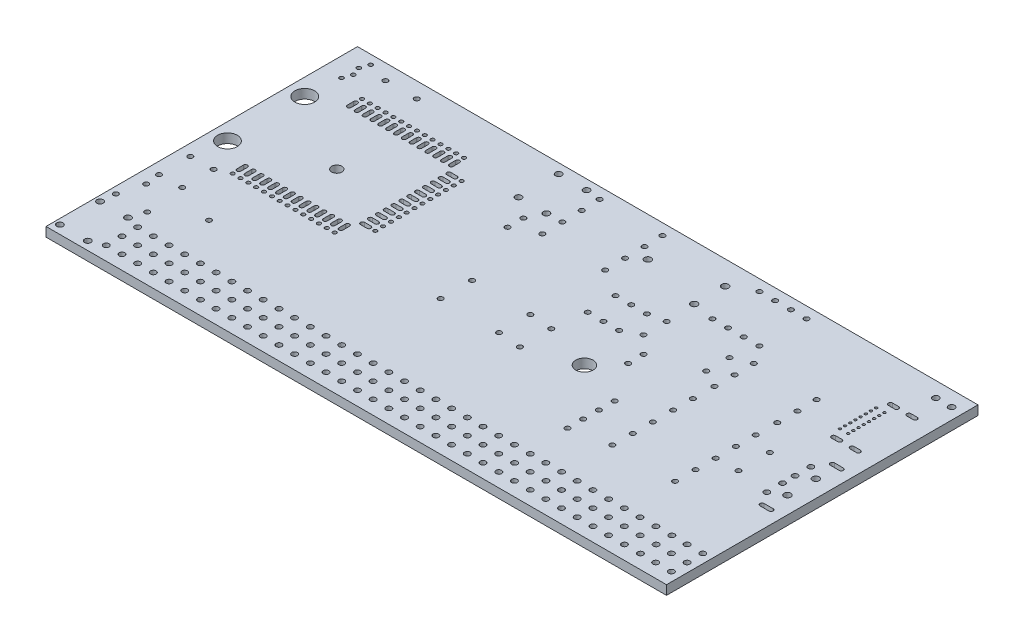
SolidWorks part; units mm, degrees
ref_plane "Front Plane" through (0, 0, 0) normal (0, 0, 1) x (1, 0, 0)
ref_plane "Top Plane" through (0, 0, 0) normal (0, 1, 0) x (1, 0, 0)
ref_plane "Right Plane" through (0, 0, 0) normal (1, 0, 0) x (0, 0, -1)
sketch "Sketch1" plane through (0, 0, 0) normal (0, 1, 0) x (1, 0, 0)
  line L0 (-55, 0) -> (55, 0) construction
  line L1 (0, -55) -> (0, 55) construction
  line B0 (9.071, 43.739) -> (9.071, 43.039) construction
  line B1 (9.071, 43.039) -> (9.071, 41.339) construction
  line B2 (28.626, 40.304) -> (27.926, 40.304) construction
  line B3 (27.926, 40.304) -> (26.226, 40.304) construction
  line B4 (1.375, 50.708) -> (1.375, 0.308)
  line B5 (1.375, 0.308) -> (101.775, 0.308)
  line B6 (101.775, 0.308) -> (101.775, 50.708)
  line B7 (101.775, 50.708) -> (1.375, 50.708)
  line B8 (9.071, 22.809) -> (9.071, 23.509) construction
  line B9 (9.071, 23.509) -> (9.071, 25.209) construction
  line B10 (99.7365, 30.632) -> (98.2815, 30.632) construction
  line B11 (98.2815, 30.632) -> (98.2815, 30.961) construction
  circle B12 centre (4.0919, 39.4542) radius 1.5922
  circle B13 centre (95.301, 42.05) radius 0.203
  circle B14 centre (95.301, 41.212) radius 0.203
  circle B15 centre (95.301, 38.697) radius 0.203
  circle B16 centre (95.301, 37.859) radius 0.203
  circle B17 centre (95.301, 40.373) radius 0.203
  circle B18 centre (95.301, 39.535) radius 0.203
  circle B19 centre (93.955, 42.05) radius 0.203
  circle B20 centre (93.955, 41.212) radius 0.203
  circle B21 centre (93.955, 40.373) radius 0.203
  circle B22 centre (93.955, 37.859) radius 0.203
  circle B23 centre (93.955, 37.02) radius 0.203
  circle B24 centre (93.955, 39.535) radius 0.203
  circle B25 centre (93.955, 38.697) radius 0.203
  circle B26 centre (96.926, 28.499) radius 0.45
  circle B27 centre (95.301, 37.02) radius 0.203
  circle B28 centre (95.301, 36.182) radius 0.203
  circle B29 centre (99.009, 27.229) radius 0.546
  circle B30 centre (99.009, 22.644) radius 0.546
  circle B31 centre (96.926, 25.959) radius 0.45
  circle B32 centre (96.926, 23.927) radius 0.45
  circle B33 centre (93.955, 36.182) radius 0.203
  circle B34 centre (88.036, 35.23) radius 0.406
  circle B35 centre (88.034, 31.965) radius 0.406
  circle B36 centre (91.618, 27.178) radius 0.406
  circle B37 centre (91.618, 22.098) radius 0.406
  circle B38 centre (88.011, 25.298) radius 0.406
  circle B39 centre (88.036, 22.003) radius 0.406
  circle B40 centre (75.844, 48.895) radius 0.406
  circle B41 centre (73.304, 48.895) radius 0.406
  circle B42 centre (75.844, 41.275) radius 0.406
  circle B43 centre (70.764, 48.895) radius 0.406
  circle B44 centre (70.764, 41.275) radius 0.406
  circle B45 centre (77.826, 38.379) radius 0.406
  circle B46 centre (87.986, 38.379) radius 0.406
  circle B47 centre (73.304, 41.275) radius 0.406
  circle B48 centre (75.057, 37.211) radius 0.406
  circle B49 centre (68.224, 48.895) radius 0.406
  circle B50 centre (64.7, 46.874) radius 0.546
  circle B51 centre (54.69, 44.374) radius 0.546
  circle B52 centre (64.68, 41.874) radius 0.546
  circle B53 centre (68.224, 41.275) radius 0.406
  circle B54 centre (64.897, 37.211) radius 0.406
  circle B55 centre (59.69, 36.678) radius 0.406
  circle B56 centre (62.23, 36.678) radius 0.406
  circle B57 centre (77.876, 35.23) radius 0.406
  circle B58 centre (77.874, 31.965) radius 0.406
  circle B59 centre (88.001, 28.512) radius 0.406
  circle B60 centre (75.057, 33.452) radius 0.406
  circle B61 centre (77.841, 28.512) radius 0.406
  circle B62 centre (77.851, 25.298) radius 0.406
  circle B63 centre (77.876, 22.003) radius 0.406
  circle B64 centre (67.666, 28.194) radius 0.406
  circle B65 centre (71.832, 21.846) radius 0.406
  circle B66 centre (64.897, 33.452) radius 0.406
  circle B67 centre (62.306, 32.106) radius 0.406
  circle B68 centre (57.15, 36.678) radius 0.406
  circle B69 centre (59.766, 32.106) radius 0.406
  circle B70 centre (67.64, 30.734) radius 0.406
  circle B71 centre (64.364, 24.435) radius 1.4
  circle B72 centre (57.226, 32.106) radius 0.406
  circle B73 centre (56.591, 26.848) radius 0.406
  circle B74 centre (96.926, 21.387) radius 0.45
  circle B75 centre (95.301, 7.645) radius 0.457
  circle B76 centre (88.011, 18.771) radius 0.406
  circle B77 centre (90.17, 7.62) radius 0.457
  circle B78 centre (97.79, 7.62) radius 0.457
  circle B79 centre (100.33, 7.62) radius 0.457
  circle B80 centre (92.735, 7.62) radius 0.457
  circle B81 centre (95.301, 5.105) radius 0.457
  circle B82 centre (77.851, 18.771) radius 0.406
  circle B83 centre (87.981, 15.489) radius 0.406
  circle B84 centre (77.821, 15.489) radius 0.406
  circle B85 centre (77.47, 7.645) radius 0.457
  circle B86 centre (85.09, 7.62) radius 0.457
  circle B87 centre (87.63, 7.62) radius 0.457
  circle B88 centre (80.01, 7.62) radius 0.457
  circle B89 centre (82.55, 7.62) radius 0.457
  circle B90 centre (100.33, 5.08) radius 0.457
  circle B91 centre (97.79, 5.08) radius 0.457
  circle B92 centre (95.301, 2.565) radius 0.457
  circle B93 centre (90.17, 5.08) radius 0.457
  circle B94 centre (92.735, 5.08) radius 0.457
  circle B95 centre (97.79, 2.54) radius 0.457
  circle B96 centre (100.33, 2.54) radius 0.457
  circle B97 centre (90.17, 2.54) radius 0.457
  circle B98 centre (92.735, 2.54) radius 0.457
  circle B99 centre (85.09, 5.08) radius 0.457
  circle B100 centre (87.63, 5.08) radius 0.457
  circle B101 centre (80.01, 5.08) radius 0.457
  circle B102 centre (82.55, 5.08) radius 0.457
  circle B103 centre (85.09, 2.54) radius 0.457
  circle B104 centre (87.63, 2.54) radius 0.457
  circle B105 centre (80.01, 2.54) radius 0.457
  circle B106 centre (82.55, 2.54) radius 0.457
  circle B107 centre (72.415, 7.62) radius 0.457
  circle B108 centre (71.832, 14.226) radius 0.406
  circle B109 centre (74.93, 7.62) radius 0.457
  circle B110 centre (71.832, 19.306) radius 0.406
  circle B111 centre (71.832, 16.766) radius 0.406
  circle B112 centre (77.47, 5.105) radius 0.457
  circle B113 centre (72.415, 5.08) radius 0.457
  circle B114 centre (69.85, 7.62) radius 0.457
  circle B115 centre (69.85, 5.08) radius 0.457
  circle B116 centre (64.77, 7.62) radius 0.457
  circle B117 centre (67.31, 7.62) radius 0.457
  circle B118 centre (56.591, 21.768) radius 0.406
  circle B119 centre (62.23, 7.62) radius 0.457
  circle B120 centre (59.69, 7.62) radius 0.457
  circle B121 centre (67.31, 5.08) radius 0.457
  circle B122 centre (54.61, 7.62) radius 0.457
  circle B123 centre (57.15, 7.62) radius 0.457
  circle B124 centre (74.93, 5.08) radius 0.457
  circle B125 centre (77.47, 2.565) radius 0.457
  circle B126 centre (64.77, 5.08) radius 0.457
  circle B127 centre (74.93, 2.54) radius 0.457
  circle B128 centre (69.85, 2.54) radius 0.457
  circle B129 centre (72.415, 2.54) radius 0.457
  circle B130 centre (64.77, 2.54) radius 0.457
  circle B131 centre (67.31, 2.54) radius 0.457
  circle B132 centre (59.69, 5.08) radius 0.457
  circle B133 centre (62.23, 5.08) radius 0.457
  circle B134 centre (54.61, 5.08) radius 0.457
  circle B135 centre (57.15, 5.08) radius 0.457
  circle B136 centre (59.69, 2.54) radius 0.457
  circle B137 centre (62.23, 2.54) radius 0.457
  circle B138 centre (54.61, 2.54) radius 0.457
  circle B139 centre (57.15, 2.54) radius 0.457
  circle B140 centre (52.629, 45.898) radius 0.406
  circle B141 centre (52.527, 48.895) radius 0.406
  circle B142 centre (42.469, 45.898) radius 0.406
  circle B143 centre (40.03, 49.124) radius 0.508
  circle B144 centre (42.367, 48.895) radius 0.406
  circle B145 centre (52.68, 42.697) radius 0.406
  circle B146 centre (52.73, 39.421) radius 0.406
  circle B147 centre (42.52, 42.697) radius 0.406
  circle B148 centre (42.57, 39.421) radius 0.406
  circle B149 centre (35.509, 49.124) radius 0.508
  circle B150 centre (40.03, 42.621) radius 0.508
  circle B151 centre (24.311, 43.739) radius 0.3
  circle B152 centre (25.581, 43.739) radius 0.3
  circle B153 centre (35.509, 42.621) radius 0.508
  circle B154 centre (38.837, 40.081) radius 0.406
  circle B155 centre (28.626, 40.304) radius 0.3
  circle B156 centre (28.626, 39.034) radius 0.3
  circle B157 centre (38.837, 37.541) radius 0.406
  circle B158 centre (28.626, 36.494) radius 0.3
  circle B159 centre (28.626, 35.224) radius 0.3
  circle B160 centre (28.626, 33.954) radius 0.3
  circle B161 centre (28.626, 32.684) radius 0.3
  circle B162 centre (43.409, 27.203) radius 0.406
  circle B163 centre (52.908, 27.153) radius 0.406
  circle B164 centre (28.626, 31.414) radius 0.3
  circle B165 centre (43.409, 22.123) radius 0.406
  circle B166 centre (28.626, 28.874) radius 0.3
  circle B167 centre (28.626, 27.604) radius 0.3
  circle B168 centre (28.626, 37.764) radius 0.3
  circle B169 centre (28.626, 30.144) radius 0.3
  circle B170 centre (28.626, 26.334) radius 0.3
  circle B171 centre (25.581, 22.809) radius 0.3
  circle B172 centre (23.041, 22.809) radius 0.3
  circle B173 centre (24.311, 22.809) radius 0.3
  circle B174 centre (16.691, 43.739) radius 0.3
  circle B175 centre (15.421, 43.739) radius 0.3
  circle B176 centre (17.961, 43.739) radius 0.3
  circle B177 centre (13.487, 48.184) radius 0.406
  circle B178 centre (14.151, 43.739) radius 0.3
  circle B179 centre (21.771, 43.739) radius 0.3
  circle B180 centre (23.041, 43.739) radius 0.3
  circle B181 centre (19.231, 43.739) radius 0.3
  circle B182 centre (20.501, 43.739) radius 0.3
  circle B183 centre (4.98, 49.219) radius 0.325
  circle B184 centre (8.407, 48.184) radius 0.406
  circle B185 centre (4.472, 47.822) radius 0.325
  circle B186 centre (4.98, 46.425) radius 0.325
  circle B187 centre (11.611, 43.739) radius 0.3
  circle B188 centre (12.881, 43.739) radius 0.3
  circle B189 centre (4.472, 45.028) radius 0.325
  circle B190 centre (9.071, 43.739) radius 0.3
  circle B191 centre (20.501, 22.809) radius 0.3
  circle B192 centre (19.231, 22.809) radius 0.3
  circle B193 centre (21.771, 22.809) radius 0.3
  circle B194 centre (16.871, 31.862) radius 0.82
  circle B195 centre (17.961, 22.809) radius 0.3
  circle B196 centre (15.421, 22.809) radius 0.3
  circle B197 centre (16.691, 22.809) radius 0.3
  circle B198 centre (12.881, 22.809) radius 0.3
  circle B199 centre (14.151, 22.809) radius 0.3
  circle B200 centre (10.341, 43.739) radius 0.3
  circle B201 centre (21.59, 5.08) radius 0.457
  circle B202 centre (24.13, 5.08) radius 0.457
  circle B203 centre (16.51, 5.08) radius 0.457
  circle B204 centre (19.05, 5.08) radius 0.457
  circle B205 centre (21.59, 2.54) radius 0.457
  circle B206 centre (24.13, 2.54) radius 0.457
  circle B207 centre (16.51, 2.54) radius 0.457
  circle B208 centre (19.05, 2.54) radius 0.457
  circle B209 centre (13.97, 5.08) radius 0.457
  circle B210 centre (13.97, 2.54) radius 0.457
  circle B211 centre (8.89, 5.08) radius 0.457
  circle B212 centre (11.43, 5.08) radius 0.457
  circle B213 centre (8.89, 2.54) radius 0.457
  circle B214 centre (11.43, 2.54) radius 0.457
  circle B215 centre (2.247, 1.676) radius 0.508
  circle B216 centre (6.768, 1.676) radius 0.508
  circle B217 centre (3.251, 21.793) radius 0.406
  circle B218 centre (3.251, 16.713) radius 0.406
  circle B219 centre (3.531, 14.351) radius 0.406
  circle B220 centre (6.768, 8.179) radius 0.508
  circle B221 centre (2.464, 10.516) radius 0.406
  circle B222 centre (2.247, 8.179) radius 0.508
  circle B223 centre (24.13, 7.62) radius 0.457
  circle B224 centre (13.691, 14.351) radius 0.406
  circle B225 centre (7.544, 10.516) radius 0.406
  circle B226 centre (13.97, 7.62) radius 0.457
  circle B227 centre (16.51, 7.62) radius 0.457
  circle B228 centre (8.89, 7.62) radius 0.457
  circle B229 centre (11.43, 7.62) radius 0.457
  circle B230 centre (6.934, 21.869) radius 0.406
  circle B231 centre (6.934, 16.789) radius 0.406
  circle B232 centre (49.53, 5.08) radius 0.457
  circle B233 centre (52.07, 5.08) radius 0.457
  circle B234 centre (44.45, 7.62) radius 0.457
  circle B235 centre (46.99, 5.08) radius 0.457
  circle B236 centre (36.83, 7.62) radius 0.457
  circle B237 centre (39.37, 7.62) radius 0.457
  circle B238 centre (26.67, 7.62) radius 0.457
  circle B239 centre (34.29, 7.62) radius 0.457
  circle B240 centre (39.37, 5.08) radius 0.457
  circle B241 centre (41.91, 5.08) radius 0.457
  circle B242 centre (29.21, 7.62) radius 0.457
  circle B243 centre (31.75, 7.62) radius 0.457
  circle B244 centre (49.53, 2.54) radius 0.457
  circle B245 centre (46.99, 2.54) radius 0.457
  circle B246 centre (52.07, 2.54) radius 0.457
  circle B247 centre (36.83, 5.08) radius 0.457
  circle B248 centre (44.45, 5.08) radius 0.457
  circle B249 centre (41.91, 2.54) radius 0.457
  circle B250 centre (44.45, 2.54) radius 0.457
  circle B251 centre (36.83, 2.54) radius 0.457
  circle B252 centre (39.37, 2.54) radius 0.457
  circle B253 centre (31.75, 5.08) radius 0.457
  circle B254 centre (34.29, 5.08) radius 0.457
  circle B255 centre (26.67, 5.08) radius 0.457
  circle B256 centre (29.21, 5.08) radius 0.457
  circle B257 centre (31.75, 2.54) radius 0.457
  circle B258 centre (34.29, 2.54) radius 0.457
  circle B259 centre (26.67, 2.54) radius 0.457
  circle B260 centre (29.21, 2.54) radius 0.457
  circle B261 centre (21.59, 7.62) radius 0.457
  circle B262 centre (19.05, 7.62) radius 0.457
  circle B263 centre (46.99, 7.62) radius 0.457
  circle B264 centre (41.91, 7.62) radius 0.457
  circle B265 centre (49.53, 7.62) radius 0.457
  circle B266 centre (11.611, 22.809) radius 0.3
  circle B267 centre (10.341, 22.809) radius 0.3
  circle B268 centre (52.07, 7.62) radius 0.457
  circle B269 centre (97.409, 48.26) radius 0.5
  circle B270 centre (9.071, 22.809) radius 0.3
  circle B271 centre (52.908, 22.073) radius 0.406
  circle B272 centre (99.949, 48.26) radius 0.5
  circle B273 centre (4.0715, 26.974) radius 1.5923
  line B274 (99.7365, 30.2952) -> (98.2815, 30.2952)
  arc B275 (98.2815, 30.9688) -> (98.2815, 30.2952) centre (98.2815, 30.632) ccw
  line B276 (99.7365, 30.9688) -> (98.2815, 30.9688)
  arc B277 (99.7365, 30.2952) -> (99.7365, 30.9688) centre (99.7365, 30.632) ccw
  line B278 (99.7365, 18.9162) -> (98.2815, 18.9162)
  arc B279 (98.2815, 19.5898) -> (98.2815, 18.9162) centre (98.2815, 19.253) ccw
  line B280 (99.7365, 19.5898) -> (98.2815, 19.5898)
  arc B281 (99.7365, 18.9162) -> (99.7365, 19.5898) centre (99.7365, 19.253) ccw
  line B282 (98.602, 43.3822) -> (97.588, 43.3822)
  arc B283 (97.588, 44.0558) -> (97.588, 43.3822) centre (97.588, 43.719) ccw
  line B284 (98.602, 44.0558) -> (97.588, 44.0558)
  arc B285 (98.602, 43.3822) -> (98.602, 44.0558) centre (98.602, 43.719) ccw
  line B286 (9.396, 42.714) -> (9.396, 41.664)
  arc B287 (8.746, 41.664) -> (9.396, 41.664) centre (9.071, 41.664) ccw
  line B288 (8.746, 42.714) -> (8.746, 41.664)
  arc B289 (9.396, 42.714) -> (8.746, 42.714) centre (9.071, 42.714) ccw
  line B290 (95.6035, 43.3771) -> (94.5895, 43.3771)
  arc B291 (94.5895, 44.0507) -> (94.5895, 43.3771) centre (94.5895, 43.7139) ccw
  line B292 (95.6035, 44.0507) -> (94.5895, 44.0507)
  arc B293 (95.6035, 43.3771) -> (95.6035, 44.0507) centre (95.6035, 43.7139) ccw
  line B294 (98.61, 34.1781) -> (97.596, 34.1781)
  arc B295 (97.596, 34.8517) -> (97.596, 34.1781) centre (97.596, 34.5149) ccw
  line B296 (98.61, 34.8517) -> (97.596, 34.8517)
  arc B297 (98.61, 34.1781) -> (98.61, 34.8517) centre (98.61, 34.5149) ccw
  line B298 (95.5977, 34.1947) -> (94.5837, 34.1947)
  arc B299 (94.5837, 34.8682) -> (94.5837, 34.1947) centre (94.5837, 34.5314) ccw
  line B300 (95.5977, 34.8682) -> (94.5837, 34.8682)
  arc B301 (95.5977, 34.1947) -> (95.5977, 34.8682) centre (95.5977, 34.5314) ccw
  line B302 (27.601, 39.979) -> (26.551, 39.979)
  arc B303 (26.551, 40.629) -> (26.551, 39.979) centre (26.551, 40.304) ccw
  line B304 (27.601, 40.629) -> (26.551, 40.629)
  arc B305 (27.601, 39.979) -> (27.601, 40.629) centre (27.601, 40.304) ccw
  line B306 (8.746, 23.834) -> (8.746, 24.884)
  arc B307 (9.396, 24.884) -> (8.746, 24.884) centre (9.071, 24.884) ccw
  line B308 (9.396, 23.834) -> (9.396, 24.884)
  arc B309 (8.746, 23.834) -> (9.396, 23.834) centre (9.071, 23.834) ccw
  line B310 (10.016, 23.834) -> (10.016, 24.884)
  arc B311 (10.666, 24.884) -> (10.016, 24.884) centre (10.341, 24.884) ccw
  line B312 (10.666, 23.834) -> (10.666, 24.884)
  arc B313 (10.016, 23.834) -> (10.666, 23.834) centre (10.341, 23.834) ccw
  line B314 (11.286, 23.834) -> (11.286, 24.884)
  arc B315 (11.936, 24.884) -> (11.286, 24.884) centre (11.611, 24.884) ccw
  line B316 (11.936, 23.834) -> (11.936, 24.884)
  arc B317 (11.286, 23.834) -> (11.936, 23.834) centre (11.611, 23.834) ccw
  line B318 (12.556, 23.834) -> (12.556, 24.884)
  arc B319 (13.206, 24.884) -> (12.556, 24.884) centre (12.881, 24.884) ccw
  line B320 (13.206, 23.834) -> (13.206, 24.884)
  arc B321 (12.556, 23.834) -> (13.206, 23.834) centre (12.881, 23.834) ccw
  line B322 (13.826, 23.834) -> (13.826, 24.884)
  arc B323 (14.476, 24.884) -> (13.826, 24.884) centre (14.151, 24.884) ccw
  line B324 (14.476, 23.834) -> (14.476, 24.884)
  arc B325 (13.826, 23.834) -> (14.476, 23.834) centre (14.151, 23.834) ccw
  line B326 (15.096, 23.834) -> (15.096, 24.884)
  arc B327 (15.746, 24.884) -> (15.096, 24.884) centre (15.421, 24.884) ccw
  line B328 (15.746, 23.834) -> (15.746, 24.884)
  arc B329 (15.096, 23.834) -> (15.746, 23.834) centre (15.421, 23.834) ccw
  line B330 (16.366, 23.834) -> (16.366, 24.884)
  arc B331 (17.016, 24.884) -> (16.366, 24.884) centre (16.691, 24.884) ccw
  line B332 (17.016, 23.834) -> (17.016, 24.884)
  arc B333 (16.366, 23.834) -> (17.016, 23.834) centre (16.691, 23.834) ccw
  line B334 (17.636, 23.834) -> (17.636, 24.884)
  arc B335 (18.286, 24.884) -> (17.636, 24.884) centre (17.961, 24.884) ccw
  line B336 (18.286, 23.834) -> (18.286, 24.884)
  arc B337 (17.636, 23.834) -> (18.286, 23.834) centre (17.961, 23.834) ccw
  line B338 (18.906, 23.834) -> (18.906, 24.884)
  arc B339 (19.556, 24.884) -> (18.906, 24.884) centre (19.231, 24.884) ccw
  line B340 (19.556, 23.834) -> (19.556, 24.884)
  arc B341 (18.906, 23.834) -> (19.556, 23.834) centre (19.231, 23.834) ccw
  line B342 (20.176, 23.834) -> (20.176, 24.884)
  arc B343 (20.826, 24.884) -> (20.176, 24.884) centre (20.501, 24.884) ccw
  line B344 (20.826, 23.834) -> (20.826, 24.884)
  arc B345 (20.176, 23.834) -> (20.826, 23.834) centre (20.501, 23.834) ccw
  line B346 (21.446, 23.834) -> (21.446, 24.884)
  arc B347 (22.096, 24.884) -> (21.446, 24.884) centre (21.771, 24.884) ccw
  line B348 (22.096, 23.834) -> (22.096, 24.884)
  arc B349 (21.446, 23.834) -> (22.096, 23.834) centre (21.771, 23.834) ccw
  line B350 (22.716, 23.834) -> (22.716, 24.884)
  arc B351 (23.366, 24.884) -> (22.716, 24.884) centre (23.041, 24.884) ccw
  line B352 (23.366, 23.834) -> (23.366, 24.884)
  arc B353 (22.716, 23.834) -> (23.366, 23.834) centre (23.041, 23.834) ccw
  line B354 (23.986, 23.834) -> (23.986, 24.884)
  arc B355 (24.636, 24.884) -> (23.986, 24.884) centre (24.311, 24.884) ccw
  line B356 (24.636, 23.834) -> (24.636, 24.884)
  arc B357 (23.986, 23.834) -> (24.636, 23.834) centre (24.311, 23.834) ccw
  line B358 (25.256, 23.834) -> (25.256, 24.884)
  arc B359 (25.906, 24.884) -> (25.256, 24.884) centre (25.581, 24.884) ccw
  line B360 (25.906, 23.834) -> (25.906, 24.884)
  arc B361 (25.256, 23.834) -> (25.906, 23.834) centre (25.581, 23.834) ccw
  line B362 (10.666, 42.714) -> (10.666, 41.664)
  arc B363 (10.016, 41.664) -> (10.666, 41.664) centre (10.341, 41.664) ccw
  line B364 (10.016, 42.714) -> (10.016, 41.664)
  arc B365 (10.666, 42.714) -> (10.016, 42.714) centre (10.341, 42.714) ccw
  line B366 (11.936, 42.714) -> (11.936, 41.664)
  arc B367 (11.286, 41.664) -> (11.936, 41.664) centre (11.611, 41.664) ccw
  line B368 (11.286, 42.714) -> (11.286, 41.664)
  arc B369 (11.936, 42.714) -> (11.286, 42.714) centre (11.611, 42.714) ccw
  line B370 (13.206, 42.714) -> (13.206, 41.664)
  arc B371 (12.556, 41.664) -> (13.206, 41.664) centre (12.881, 41.664) ccw
  line B372 (12.556, 42.714) -> (12.556, 41.664)
  arc B373 (13.206, 42.714) -> (12.556, 42.714) centre (12.881, 42.714) ccw
  line B374 (14.476, 42.714) -> (14.476, 41.664)
  arc B375 (13.826, 41.664) -> (14.476, 41.664) centre (14.151, 41.664) ccw
  line B376 (13.826, 42.714) -> (13.826, 41.664)
  arc B377 (14.476, 42.714) -> (13.826, 42.714) centre (14.151, 42.714) ccw
  line B378 (15.746, 42.714) -> (15.746, 41.664)
  arc B379 (15.096, 41.664) -> (15.746, 41.664) centre (15.421, 41.664) ccw
  line B380 (15.096, 42.714) -> (15.096, 41.664)
  arc B381 (15.746, 42.714) -> (15.096, 42.714) centre (15.421, 42.714) ccw
  line B382 (17.016, 42.714) -> (17.016, 41.664)
  arc B383 (16.366, 41.664) -> (17.016, 41.664) centre (16.691, 41.664) ccw
  line B384 (16.366, 42.714) -> (16.366, 41.664)
  arc B385 (17.016, 42.714) -> (16.366, 42.714) centre (16.691, 42.714) ccw
  line B386 (18.286, 42.714) -> (18.286, 41.664)
  arc B387 (17.636, 41.664) -> (18.286, 41.664) centre (17.961, 41.664) ccw
  line B388 (17.636, 42.714) -> (17.636, 41.664)
  arc B389 (18.286, 42.714) -> (17.636, 42.714) centre (17.961, 42.714) ccw
  line B390 (19.556, 42.714) -> (19.556, 41.664)
  arc B391 (18.906, 41.664) -> (19.556, 41.664) centre (19.231, 41.664) ccw
  line B392 (18.906, 42.714) -> (18.906, 41.664)
  arc B393 (19.556, 42.714) -> (18.906, 42.714) centre (19.231, 42.714) ccw
  line B394 (20.826, 42.714) -> (20.826, 41.664)
  arc B395 (20.176, 41.664) -> (20.826, 41.664) centre (20.501, 41.664) ccw
  line B396 (20.176, 42.714) -> (20.176, 41.664)
  arc B397 (20.826, 42.714) -> (20.176, 42.714) centre (20.501, 42.714) ccw
  line B398 (22.096, 42.714) -> (22.096, 41.664)
  arc B399 (21.446, 41.664) -> (22.096, 41.664) centre (21.771, 41.664) ccw
  line B400 (21.446, 42.714) -> (21.446, 41.664)
  arc B401 (22.096, 42.714) -> (21.446, 42.714) centre (21.771, 42.714) ccw
  line B402 (23.366, 42.714) -> (23.366, 41.664)
  arc B403 (22.716, 41.664) -> (23.366, 41.664) centre (23.041, 41.664) ccw
  line B404 (22.716, 42.714) -> (22.716, 41.664)
  arc B405 (23.366, 42.714) -> (22.716, 42.714) centre (23.041, 42.714) ccw
  line B406 (24.636, 42.714) -> (24.636, 41.664)
  arc B407 (23.986, 41.664) -> (24.636, 41.664) centre (24.311, 41.664) ccw
  line B408 (23.986, 42.714) -> (23.986, 41.664)
  arc B409 (24.636, 42.714) -> (23.986, 42.714) centre (24.311, 42.714) ccw
  line B410 (25.906, 42.714) -> (25.906, 41.664)
  arc B411 (25.256, 41.664) -> (25.906, 41.664) centre (25.581, 41.664) ccw
  line B412 (25.256, 42.714) -> (25.256, 41.664)
  arc B413 (25.906, 42.714) -> (25.256, 42.714) centre (25.581, 42.714) ccw
  line B414 (27.601, 38.709) -> (26.551, 38.709)
  arc B415 (26.551, 39.359) -> (26.551, 38.709) centre (26.551, 39.034) ccw
  line B416 (27.601, 39.359) -> (26.551, 39.359)
  arc B417 (27.601, 38.709) -> (27.601, 39.359) centre (27.601, 39.034) ccw
  line B418 (27.601, 37.439) -> (26.551, 37.439)
  arc B419 (26.551, 38.089) -> (26.551, 37.439) centre (26.551, 37.764) ccw
  line B420 (27.601, 38.089) -> (26.551, 38.089)
  arc B421 (27.601, 37.439) -> (27.601, 38.089) centre (27.601, 37.764) ccw
  line B422 (27.601, 36.169) -> (26.551, 36.169)
  arc B423 (26.551, 36.819) -> (26.551, 36.169) centre (26.551, 36.494) ccw
  line B424 (27.601, 36.819) -> (26.551, 36.819)
  arc B425 (27.601, 36.169) -> (27.601, 36.819) centre (27.601, 36.494) ccw
  line B426 (27.601, 34.899) -> (26.551, 34.899)
  arc B427 (26.551, 35.549) -> (26.551, 34.899) centre (26.551, 35.224) ccw
  line B428 (27.601, 35.549) -> (26.551, 35.549)
  arc B429 (27.601, 34.899) -> (27.601, 35.549) centre (27.601, 35.224) ccw
  line B430 (27.601, 33.629) -> (26.551, 33.629)
  arc B431 (26.551, 34.279) -> (26.551, 33.629) centre (26.551, 33.954) ccw
  line B432 (27.601, 34.279) -> (26.551, 34.279)
  arc B433 (27.601, 33.629) -> (27.601, 34.279) centre (27.601, 33.954) ccw
  line B434 (27.601, 32.359) -> (26.551, 32.359)
  arc B435 (26.551, 33.009) -> (26.551, 32.359) centre (26.551, 32.684) ccw
  line B436 (27.601, 33.009) -> (26.551, 33.009)
  arc B437 (27.601, 32.359) -> (27.601, 33.009) centre (27.601, 32.684) ccw
  line B438 (27.601, 31.089) -> (26.551, 31.089)
  arc B439 (26.551, 31.739) -> (26.551, 31.089) centre (26.551, 31.414) ccw
  line B440 (27.601, 31.739) -> (26.551, 31.739)
  arc B441 (27.601, 31.089) -> (27.601, 31.739) centre (27.601, 31.414) ccw
  line B442 (27.601, 29.819) -> (26.551, 29.819)
  arc B443 (26.551, 30.469) -> (26.551, 29.819) centre (26.551, 30.144) ccw
  line B444 (27.601, 30.469) -> (26.551, 30.469)
  arc B445 (27.601, 29.819) -> (27.601, 30.469) centre (27.601, 30.144) ccw
  line B446 (27.601, 28.549) -> (26.551, 28.549)
  arc B447 (26.551, 29.199) -> (26.551, 28.549) centre (26.551, 28.874) ccw
  line B448 (27.601, 29.199) -> (26.551, 29.199)
  arc B449 (27.601, 28.549) -> (27.601, 29.199) centre (27.601, 28.874) ccw
  line B450 (27.601, 27.279) -> (26.551, 27.279)
  arc B451 (26.551, 27.929) -> (26.551, 27.279) centre (26.551, 27.604) ccw
  line B452 (27.601, 27.929) -> (26.551, 27.929)
  arc B453 (27.601, 27.279) -> (27.601, 27.929) centre (27.601, 27.604) ccw
  line B454 (27.601, 26.009) -> (26.551, 26.009)
  arc B455 (26.551, 26.659) -> (26.551, 26.009) centre (26.551, 26.334) ccw
  line B456 (27.601, 26.659) -> (26.551, 26.659)
  arc B457 (27.601, 26.009) -> (27.601, 26.659) centre (27.601, 26.334) ccw
  dimension "D1" = 0.308
  dimension "D2" = 1.375
sketch_block_instance "Block1-1"
sketch_block "Block1" parameters "D1"=100.4, "D2"=50.4, "D3"=1.455, "D4"=0.329
extrude "Boss-Extrude1" add sketch "Sketch1" along normal blind 1.5
sketch "cmp traces"
sketch "Sol traces"
